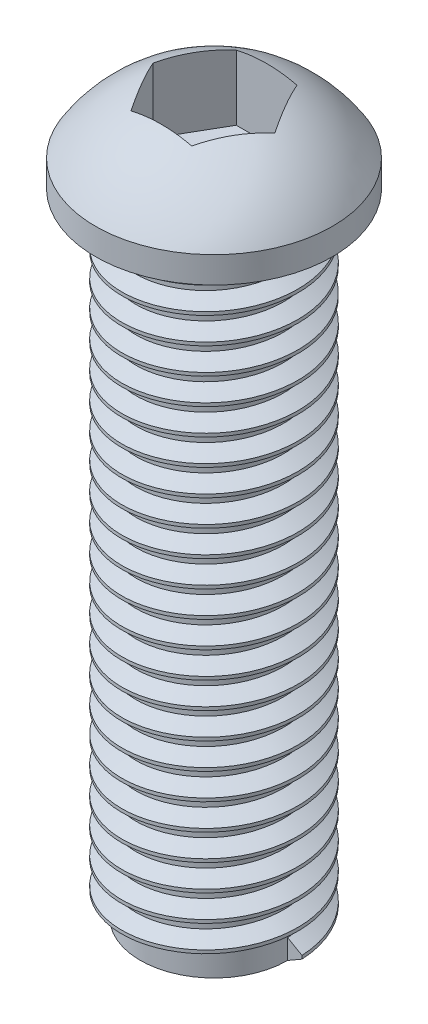
SolidWorks part; units mm, degrees
ref_plane "Front Plane" through (0, 0, 0) normal (0, 0, 1) x (1, 0, 0)
ref_plane "Top Plane" through (0, 0, 0) normal (0, 1, 0) x (1, 0, 0)
ref_plane "Right Plane" through (0, 0, 0) normal (1, 0, 0) x (0, 0, -1)
sketch "Sketch1" plane through (0, 0, 0) normal (0, 1, 0) x (1, 0, 0)
  circle A0 centre (0, 0) radius 1.4
  dimension "D1" = 2.8
extrude "Boss-Extrude1" add sketch "Sketch1" against normal blind 12
sketch "Sketch2" plane through (0, 0, 0) normal (0, 0, 1) x (1, 0, 0)
  line L0 (0, 0) -> (2.25, 0)
  line L1 (2.25, 0) -> (2.25, 0.5)
  line L2 (0, 0) -> (0, 1.75)
  arc A0 (0, 1.75) -> (2.25, 0.5) centre (0, -0.9) cw
  dimension "D1" = 2.25
  dimension "D2" = 0.5
  dimension "D3" = 1.75
revolve "Revolve1" add sketch "Sketch2" angle 360 about L2
sketch "Sketch3" plane through (0, 0, 0) normal (0, 1, 0) x (1, 0, 0)
  line L1 (1.1547, 0) -> (0.5774, 1)
  line L2 (0.5774, 1) -> (-0.5774, 1)
  line L3 (-0.5774, 1) -> (-1.1547, 0)
  line L4 (-1.1547, 0) -> (-0.5774, -1)
  line L5 (-0.5774, -1) -> (0.5774, -1)
  line L6 (0.5774, -1) -> (1.1547, 0)
  circle A0 centre (0, 0) radius 1 construction
  dimension "D1" = 2
  dimension "D2" = 1
extrude "Cut-Extrude1" cut sketch "Sketch3" against normal blind 1.5 from offset 1.75
thread "Thread2" pitch 0.5 method extrude profile "Thread Profile2" start angle 0, offset 0, length 0, pitch 0.5, diameter 2.8
ref_plane "Plane2" through (1.4, -12, 0) normal (0, 0, 1) x (1, 0, 0)
sketch "Thread Profile2" plane through (1.4, -12, 0) normal (0, 0, 1) x (1, 0, 0)
  line L0 (0, 0) -> (0, 0.5) construction
  line L1 (0, 0) -> (0.2706, 0.1562)
  line L2 (0.2706, 0.1562) -> (0.2706, 0.2187)
  line L3 (0.2706, 0.2187) -> (0, 0.375)
  line L4 (0.2706, 0.1875) -> (0, 0.1875) construction
  line L11 (0, 0) -> (0, 0.375)
  point P2 (0, 0)
  dimension "Pitch" = 0.5
  dimension "Profile_Angle" = 60
  dimension "Profile_Land" = 0.0625
  dimension "Profile_Height" = 0.2706
